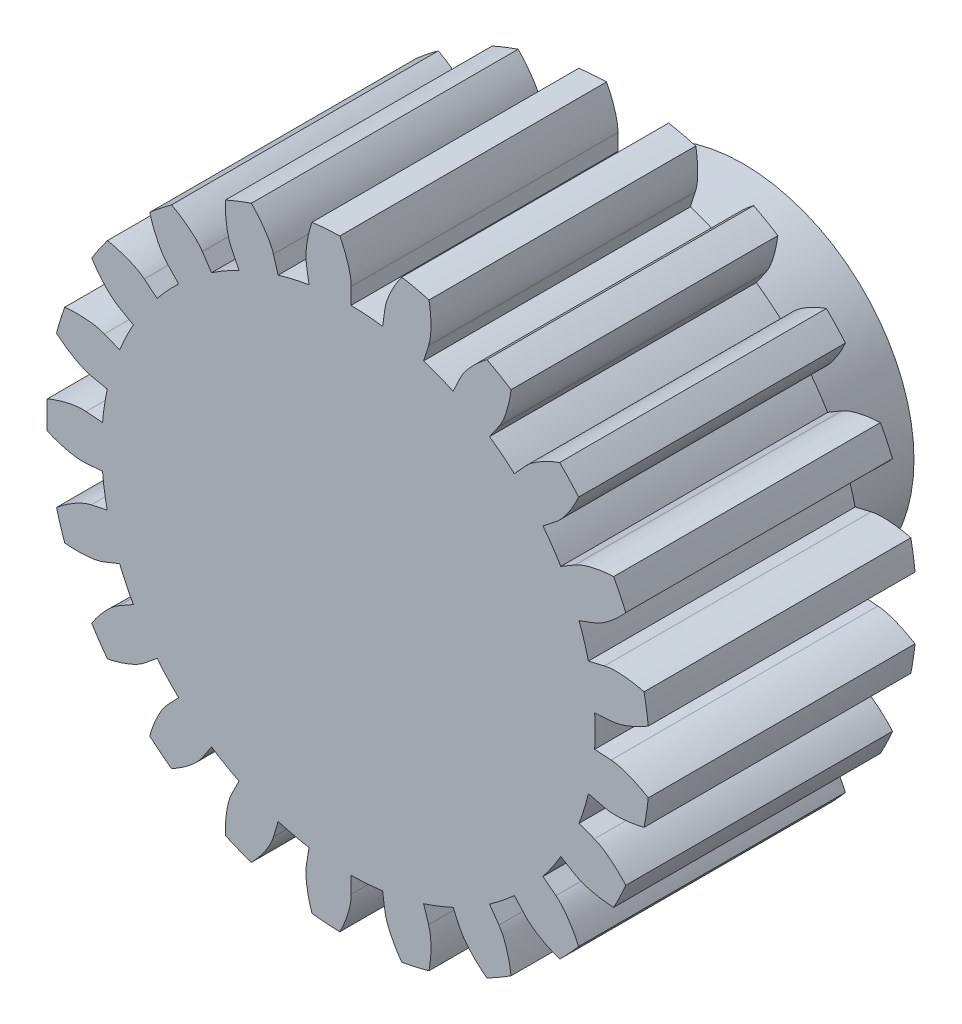
SolidWorks part; units mm, degrees
ref_plane "前视基准面" through (0, 0, 0) normal (0, 0, 1) x (1, 0, 0)
ref_plane "上视基准面" through (0, 0, 0) normal (0, 1, 0) x (1, 0, 0)
ref_plane "右视基准面" through (0, 0, 0) normal (1, 0, 0) x (0, 0, -1)
other "Configuration Table"
sketch "草图1" plane through (0, 0, 0) normal (0, 0, 1) x (1, 0, 0)
  line L0 (0, 0) -> (5.25, 0) construction
  line L1 (0, 0) -> (5.2353, 0.3923) construction
  line L2 (0, 0) -> (4.9232, 0.3169)
  line L3 (5.2353, 0.3923) -> (5.2353, -0.3923) construction
  line L4 (0, 0) -> (4.9232, -0.3169)
  circle A0 centre (0, 0) radius 5.75
  circle A1 centre (0, 0) radius 5.25 construction
  circle A2 centre (0, 0) radius 4.625
  circle A3 centre (0, 0) radius 4.9334 construction
  circle A4 centre (0, 0) radius 1.475
  spline S0 degree 4 poles (4.9232, 0.3169) (4.9607, 0.3193) (5.065, 0.3339) (5.2581, 0.3925) (5.555, 0.5296) (5.9082, 0.7653) (6.3141, 1.1289) (6.7208, 1.6221) (7.0851, 2.222) (7.4595, 3.0902) (7.6869, 4.0103) (7.7831, 4.9894) (7.7375, 6.1592) (7.5421, 7.3154) (7.1213, 8.6118) (6.437, 9.9622) (5.566, 11.1996) (4.5364, 12.3078) (3.3742, 13.2753) (2.1035, 14.0945) (0.7466, 14.7607) (-0.4976, 15.2081) (-1.5022, 15.4709) (-2.2418, 15.6171) (-2.7079, 15.6926) (-3.0798, 15.7435) (-3.4583, 15.7849) (-3.8273, 15.8169) (-4.1819, 15.8376) (-4.4716, 15.8494) (-4.8011, 15.8553) (-5.0151, 15.8558) (-5.3597, 15.8515) (-5.6291, 15.8407) (-5.9536, 15.8242) (-6.2447, 15.8018) (-6.5555, 15.7736) (-6.8526, 15.7397) (-7.0823, 15.71) (-7.2316, 15.6883) (-7.3069, 15.677) knots 0 0 0 0 0 0.005604 0.015718 0.02996 0.048734 0.068727 0.096889 0.125051 0.153212 0.209535 0.237696 0.271429 0.327752 0.384075 0.440398 0.496721 0.553044 0.609367 0.66569 0.722013 0.778336 0.806497 0.820578 0.834659 0.84874 0.86282 0.876901 0.890982 0.900036 0.909091 0.920455 0.931818 0.943182 0.954545 0.965909 0.977273 0.988636 1 1 1 1 1 construction
  spline S1 degree 4 poles (4.9232, 0.3169) (4.9607, 0.3193) (5.065, 0.3339) (5.2581, 0.3925) (5.555, 0.5296) (5.9082, 0.7653) (6.3141, 1.1289) (6.7208, 1.6221) (7.0851, 2.222) (7.4595, 3.0902) (7.6869, 4.0103) (7.7831, 4.9894) (7.7375, 6.1592) (7.5421, 7.3154) (7.1213, 8.6118) (6.437, 9.9622) (5.566, 11.1996) (4.5364, 12.3078) (3.3742, 13.2753) (2.1035, 14.0945) (0.7466, 14.7607) (-0.4976, 15.2081) (-1.5022, 15.4709) (-2.2418, 15.6171) (-2.7079, 15.6926) (-3.0798, 15.7435) (-3.4583, 15.7849) (-3.8273, 15.8169) (-4.1819, 15.8376) (-4.4716, 15.8494) (-4.7152, 15.8537) (-4.8263, 15.8548) (-4.8814, 15.855) knots 0 0 0 0 0 0.005604 0.015718 0.02996 0.048734 0.068727 0.096889 0.125051 0.153212 0.209535 0.237696 0.271429 0.327752 0.384075 0.440398 0.496721 0.553044 0.609367 0.66569 0.722013 0.778336 0.806497 0.820578 0.834659 0.84874 0.86282 0.876901 0.890982 0.900036 0.909091 0.909091 0.909091 0.909091 0.909091
  spline S2 degree 4 poles (4.9232, -0.3169) (4.9607, -0.3193) (5.065, -0.3339) (5.2581, -0.3925) (5.555, -0.5296) (5.9082, -0.7653) (6.3141, -1.1289) (6.7208, -1.6221) (7.0851, -2.222) (7.4595, -3.0902) (7.6869, -4.0103) (7.7831, -4.9894) (7.7375, -6.1592) (7.5421, -7.3154) (7.1213, -8.6118) (6.437, -9.9622) (5.566, -11.1996) (4.5364, -12.3078) (3.3742, -13.2753) (2.1035, -14.0945) (0.7466, -14.7607) (-0.4976, -15.2081) (-1.5022, -15.4709) (-2.2418, -15.6171) (-2.7079, -15.6926) (-3.0798, -15.7435) (-3.4583, -15.7849) (-3.8273, -15.8169) (-4.1819, -15.8376) (-4.4716, -15.8494) (-4.8011, -15.8553) (-5.0151, -15.8558) (-5.3597, -15.8515) (-5.6291, -15.8407) (-5.9536, -15.8242) (-6.2447, -15.8018) (-6.5555, -15.7736) (-6.8526, -15.7397) (-7.0823, -15.71) (-7.2316, -15.6883) (-7.3069, -15.677) knots 0 0 0 0 0 0.005604 0.015718 0.02996 0.048734 0.068727 0.096889 0.125051 0.153212 0.209535 0.237696 0.271429 0.327752 0.384075 0.440398 0.496721 0.553044 0.609367 0.66569 0.722013 0.778336 0.806497 0.820578 0.834659 0.84874 0.86282 0.876901 0.890982 0.900036 0.909091 0.920455 0.931818 0.943182 0.954545 0.965909 0.977273 0.988636 1 1 1 1 1 construction
  spline S3 degree 4 poles (4.9232, -0.3169) (4.9607, -0.3193) (5.065, -0.3339) (5.2581, -0.3925) (5.555, -0.5296) (5.9082, -0.7653) (6.3141, -1.1289) (6.7208, -1.6221) (7.0851, -2.222) (7.4595, -3.0902) (7.6869, -4.0103) (7.7831, -4.9894) (7.7375, -6.1592) (7.5421, -7.3154) (7.1213, -8.6118) (6.437, -9.9622) (5.566, -11.1996) (4.5364, -12.3078) (3.3742, -13.2753) (2.1035, -14.0945) (0.7466, -14.7607) (-0.4976, -15.2081) (-1.5022, -15.4709) (-2.2418, -15.6171) (-2.7079, -15.6926) (-3.0798, -15.7435) (-3.4583, -15.7849) (-3.8273, -15.8169) (-4.1819, -15.8376) (-4.4716, -15.8494) (-4.7152, -15.8537) (-4.8263, -15.8548) (-4.8814, -15.855) knots 0 0 0 0 0 0.005604 0.015718 0.02996 0.048734 0.068727 0.096889 0.125051 0.153212 0.209535 0.237696 0.271429 0.327752 0.384075 0.440398 0.496721 0.553044 0.609367 0.66569 0.722013 0.778336 0.806497 0.820578 0.834659 0.84874 0.86282 0.876901 0.890982 0.900036 0.909091 0.909091 0.909091 0.909091 0.909091
  point P15 (5.2353, 0)
  dimension "齿顶圆直径" = 11.5
  dimension "分度圆直径" = 10.5
  dimension "齿根圆直径" = 9.25
  dimension "基圆直径" = 9.8668
  dimension "内孔直径" = 2.95
  dimension "渐近线镜像线夹角" = 4.286
extrude "凸台-拉伸1" add sketch "草图1" along normal blind 5 contours A0 | A4
extrude "切除-拉伸1" cut sketch "草图1<3>" along normal through all contours A2 S3 A0 S1 region at (5.2601, 0, 0)
sketch "草图1<3>" plane through (0, 0, 0) normal (0, 0, 1) x (1, 0, 0) same geometry as "草图1"
pattern_circular "阵列(圆周)1" count 21 every 17.143 about axis through (0, 0, 5) along (0, 0, 1) of "切除-拉伸1"
sketch "草图2" plane through (0, 0, 5) normal (0, 0, 1) x (1, 0, 0)
  circle A0 centre (0, 0) radius 1.475
extrude "凸台-拉伸2" add sketch "草图2" against normal through all
sketch "草图3" plane through (0, 0, 0) normal (0, 0, -1) x (-1, 0, 0)
  line L1 (0.6, 1.0392) -> (-0.6, 1.0392)
  line L2 (-0.6, 1.0392) -> (-1.2, 0)
  line L3 (-1.2, 0) -> (-0.6, -1.0392)
  line L4 (-0.6, -1.0392) -> (0.6, -1.0392)
  line L5 (0.6, -1.0392) -> (1.2, 0)
  line L6 (1.2, 0) -> (0.6, 1.0392)
  circle A0 centre (0, 0) radius 2.2
  circle A1 centre (0, 0) radius 3.2
  circle A2 centre (0, 0) radius 1.0392 construction
  dimension "D1" = 1
  dimension "D2" = 4.4
  dimension "D3" = 1.2
extrude "凸台-拉伸3" add sketch "草图3" along normal blind 2.4 contours A1 A0 | L5 L6 L1 L2 L3 L4 region at (0, 0, 0) region at (3.1095, 0, 0)
sketch "草图4" plane through (0, 0, 5) normal (0, 0, 1) x (1, 0, 0)
  line L0 (1, 1.118) -> (1, -1.118)
  circle A0 centre (0, 0) radius 1.5
  dimension "D1" = 3
  dimension "D2" = 1
sketch "草图5" plane through (0, 0, -2.4) normal (0, 0, -1) x (-1, 0, 0)
  circle A0 centre (0, 0) radius 1.2
extrude "切除-拉伸2" cut sketch "草图5" against normal blind 1
sketch "草图6" plane through (0, 0, 5) normal (0, 0, 1) x (1, 0, 0)
  circle A0 centre (0, 0) radius 5.65
  arc A1 (1.0678, -5.65) -> (1.4894, -5.5538) centre (0, 0) ccw construction
  point P2 (0, 0)
  point P3 (0.7493, -2.6164)
  dimension "D1" = 0.1
extrude "切除-拉伸3" cut sketch "草图6" against normal through all flip side to cut
equation "\"m\"= 0.5'模数"
equation "\"z\"= 21'齿数"
equation "\"a\"= 20度'压力角"
equation "\"d\"= \"m\" * \"z\"'分度圆直径"
equation "\"da\"= ( \"z\" + 2 ) * \"m\"'齿顶圆直径"
equation "\"df\"= ( \"z\" - 2.5 ) * \"m\"'齿根圆直径"
equation "\"s\"= 0.5 * PI * \"m\"'分度圆齿厚"
equation "\"r\"= 0.38 * \"m\"'齿根圆角"
equation "\"B\"= 0.3 * \"d\"'齿厚"
equation "\"db\"= \"m\" * \"z\" * cos ( \"a\" )'基圆直径"
equation "\"rb\"= \"db\" / 2'基圆半径"
equation "\"齿顶圆直径@草图1\"= \"da\""
equation "\"分度圆直径@草图1\"= \"d\""
equation "\"齿根圆直径@草图1\"= \"df\""
equation "\"基圆直径@草图1\"= \"db\""
equation "\"渐近线镜像线夹角@草图1\"= 360 / 4 / \"z\""
equation "\"h\"= 5'齿轮厚度"
equation "\"ir\"= 2.95'内孔直径"
equation "\"内孔直径@草图1\"= \"ir\""
equation "\"齿轮厚@凸台-拉伸1\"= \"h\""
equation "\"齿轮夹角@阵列(圆周)1\"= 360 / \"z\""
equation "\"齿数@阵列(圆周)1\"= \"z\""
